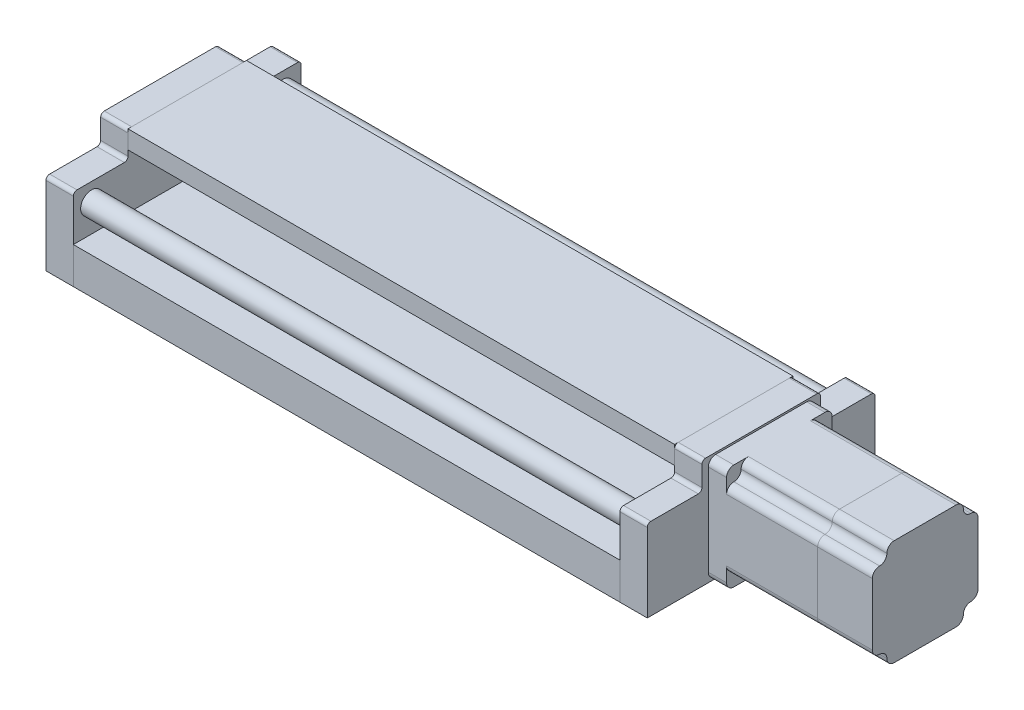
SolidWorks part; units mm, degrees
ref_plane "Front Plane" through (0, 0, 0) normal (0, 0, 1) x (1, 0, 0)
ref_plane "Top Plane" through (0, 0, 0) normal (0, 1, 0) x (1, 0, 0)
ref_plane "Right Plane" through (0, 0, 0) normal (1, 0, 0) x (0, 0, -1)
sketch "Sketch1" plane through (0, 0, 0) normal (0, 1, 0) x (1, 0, 0)
  line L1 (-150, 62.5) -> (150, 62.5)
  line L2 (-150, 62.5) -> (-150, -62.5)
  line L3 (-150, -62.5) -> (150, -62.5)
  line L4 (150, 62.5) -> (150, -62.5)
  line L5 (-150, 62.5) -> (150, -62.5) construction
  line L6 (-150, -62.5) -> (150, 62.5) construction
  point P0 (0, 0)
  dimension "D1" = 300
  dimension "D2" = 125
extrude "Boss-Extrude1" add sketch "Sketch1" along normal blind 20
sketch "Sketch2" plane through (150, 0, 0) normal (1, 0, 0) x (0, 0, -1)
  line L0 (-62.5, 20) -> (-62.5, 45)
  line L1 (-62.5, 45) -> (-32.5, 45)
  line L2 (-32.5, 45) -> (-32.5, 60)
  line L3 (-32.5, 60) -> (32.5, 60)
  line L4 (32.5, 60) -> (32.5, 45)
  line L5 (32.5, 45) -> (62.5, 45)
  line L6 (62.5, 45) -> (62.5, 20)
  line M6 (-62.5, 0) -> (62.5, 0)
  line M7 (62.5, 0) -> (62.5, 20)
  line M8 (62.5, 20) -> (-62.5, 20)
  line M9 (-62.5, 20) -> (-62.5, 0)
  dimension "D1" = 25
  dimension "D2" = 15
  dimension "D3" = 30
extrude "Boss-Extrude2" add sketch "Sketch2" along normal blind 15 separate body contours L6 L5 L4 L3 L2 L1 L0 M8 | M9 M6 M7 M8 region at (150, 37.2561, 0) region at (150, 10, 0)
mirror "Mirror1" about plane through (0, 0, 0) normal (1, 0, 0) of bodies 102
sketch "Sketch3" plane through (-150, 0, 0) normal (1, 0, 0) x (0, 0, -1)
  line L0 (-62.5, 0) -> (-62.5, 45) construction
  line L1 (-62.5, 45) -> (-32.5, 45) construction
  circle A0 centre (-52.5, 35) radius 6
  dimension "D1" = 12
  dimension "D2" = 10
  dimension "D3" = 10
extrude "Boss-Extrude3" add sketch "Sketch3" along normal up to surface (300 mm away) separate body up to face at (150, 37.5, 0)
mirror "Mirror2" about plane through (0, 0, 0) normal (0, 0, 1) of bodies 104
sketch "Sketch4" plane through (165, 0, 0) normal (1, 0, 0) x (0, 0, -1)
  line L1 (-29, 59) -> (29, 59)
  line L2 (-29, 59) -> (-29, 1)
  line L3 (-29, 1) -> (29, 1)
  line L4 (29, 59) -> (29, 1)
  line L5 (-29, 59) -> (29, 1) construction
  line L6 (-29, 1) -> (29, 59) construction
  line L7 (-32.5, 60) -> (32.5, 60) construction
  point P0 (0, 30)
  point P5 (0, 22.6158)
  point P7 (0, 0)
  point P9 (0, 32.5)
  dimension "D1" = 58
  dimension "D2" = 30
extrude "Boss-Extrude4" add sketch "Sketch4" along normal blind 10
sketch "Sketch5" plane through (175, 0, 0) normal (1, 0, 0) x (0, 0, -1)
  line L0 (-21, 59) -> (-21, 51)
  line L1 (29, 59) -> (-29, 59) construction
  line L2 (-21, 51) -> (-29, 51)
  line L3 (-29, 59) -> (-29, 1) construction
  line L4 (21, 59) -> (21, 51)
  line L5 (21, 51) -> (29, 51)
  line L6 (29, 1) -> (29, 59) construction
  line L7 (21, 1) -> (21, 9)
  line L8 (21, 9) -> (29, 9)
  line L10 (-29, 9) -> (-21, 9)
  line L11 (-29, 59) -> (-29, 1) construction
  line L12 (-21, 9) -> (-21, 1)
  line L13 (-29, 1) -> (29, 1) construction
  line L14 (29, 1) -> (29, 59) construction
  line M6 (29, 1) -> (29, 59)
  line M7 (29, 59) -> (-29, 59)
  line M8 (-29, 59) -> (-29, 1)
  line M9 (-29, 1) -> (29, 1)
  dimension "D1" = 8
extrude "Boss-Extrude5" add sketch "Sketch5" along normal blind 50 contours L10 L12 L7 L8 L5 L4 L0 L2 M9 M6 M7 M8 region at (175, 30, 0)
sketch "Sketch6" plane through (225, 0, 0) normal (1, 0, 0) x (0, 0, -1)
  line L12 (-29, 9) -> (-21, 9)
  line L13 (-21, 9) -> (-21, 1)
  line L14 (-21, 1) -> (21, 1)
  line L15 (21, 1) -> (21, 9)
  line L16 (21, 9) -> (29, 9)
  line L17 (29, 9) -> (29, 51)
  line L18 (29, 51) -> (21, 51)
  line L19 (21, 51) -> (21, 59)
  line L20 (21, 59) -> (-21, 59)
  line L21 (-21, 59) -> (-21, 51)
  line L22 (-21, 51) -> (-29, 51)
  line L23 (-29, 51) -> (-29, 9)
  line L24 (-29, 9) -> (-21, 9)
  line L25 (-21, 9) -> (-21, 1)
  line L26 (-21, 1) -> (21, 1)
  line L27 (21, 1) -> (21, 9)
  line L28 (21, 9) -> (29, 9)
  line L29 (29, 9) -> (29, 51)
  line L30 (29, 51) -> (21, 51)
  line L31 (21, 51) -> (21, 59)
  line L32 (21, 59) -> (-21, 59)
  line L33 (-21, 59) -> (-21, 51)
  line L34 (-21, 51) -> (-29, 51)
  line L35 (-29, 51) -> (-29, 9)
  dimension "D1" = 0
extrude "Boss-Extrude6" add sketch "Sketch6" along normal blind 30 separate body
sketch "Sketch7" plane through (-150, 0, 0) normal (1, 0, 0) x (0, 0, -1)
  line L0 (-32.5, 50) -> (32.5, 50)
  line L1 (-32.5, 45) -> (-32.5, 60) construction
  line L2 (32.5, 60) -> (32.5, 45) construction
  line L3 (-32.5, 60) -> (32.5, 60) construction
  line M4 (32.5, 45) -> (32.5, 60)
  line M5 (32.5, 60) -> (-32.5, 60)
  line M6 (-32.5, 60) -> (-32.5, 45)
  dimension "D1" = 10
extrude "Boss-Extrude7" add sketch "Sketch7" along normal up to surface (300 mm away) separate body contours L0 M6 M4 M5 region at (-150, 55, 0) up to face at (150, 37.5, 0)
fillet "Fillet1" radius 2 6 edges at (-157.5, 45, 32.5) (-157.5, 45, -32.5) (-157.5, 45, -62.5) (-157.5, 60, -32.5) (-157.5, 60, 32.5) (-157.5, 45, 62.5)
fillet "Fillet2" radius 2 6 edges at (157.5, 45, -62.5) (157.5, 45, -32.5) (157.5, 60, -32.5) (157.5, 45, 32.5) (157.5, 60, 32.5) (157.5, 45, 62.5)
fillet "Fillet3" radius 4 16 edges at (170, 1, 29) (170, 1, -29) (170, 59, 29) (170, 59, -29) (200, 51, -21) (200, 9, -21) (200, 9, 21) (200, 51, 21) (200, 9, 29) (200, 1, 21) (200, 1, -21) (200, 9, -29) (200, 51, -29) (200, 59, -21) (200, 51, 29) (200, 59, 21)
fillet "Fillet4" radius 4 12 edges at (240, 1, -21) (240, 51, 29) (240, 9, 29) (240, 1, 21) (240, 9, -29) (240, 51, -29) (240, 59, -21) (240, 59, 21) (240, 9, -21) (240, 9, 21) (240, 51, -21) (240, 51, 21)
